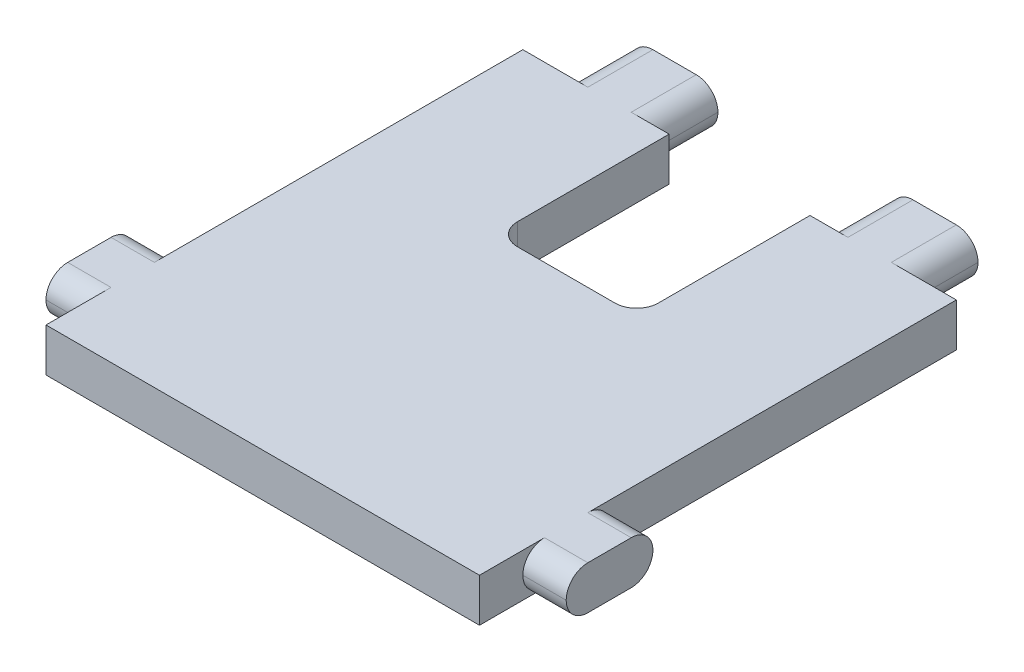
SolidWorks part; units mm, degrees
ref_plane "Front Plane" through (0, 0, 0) normal (0, 0, 1) x (1, 0, 0)
ref_plane "Top Plane" through (0, 0, 0) normal (0, 1, 0) x (1, 0, 0)
ref_plane "Right Plane" through (0, 0, 0) normal (1, 0, 0) x (0, 0, -1)
sketch "Sketch1" plane through (0, 0, 0) normal (0, 1, 0) x (1, 0, 0)
  line L0 (0, 11) -> (0, -11) construction
  line L1 (10, 11) -> (-10, 11)
  line L2 (10, 11) -> (10, -11)
  line L3 (10, -11) -> (-10, -11)
  line L4 (-10, 11) -> (-10, -11)
  line L5 (10, 11) -> (-10, -11) construction
  line L6 (10, -11) -> (-10, 11) construction
  line L15 (10, -9) -> (10, -5)
  line L21 (-3.25, 3) -> (3.25, 3)
  line L22 (-10, -9) -> (-12, -9)
  line L23 (-10, -9) -> (-10, -5)
  line L24 (-10, -5) -> (-12, -5)
  line L25 (-12, -9) -> (-12, -5)
  line L26 (10, -9) -> (12, -9)
  line L27 (12, -9) -> (12, -5)
  line L28 (10, -5) -> (12, -5)
  line L29 (-3.25, 3) -> (-3.25, 11)
  line L30 (-3.25, 11) -> (3.25, 11)
  line L31 (3.25, 3) -> (3.25, 11)
  line L32 (-3.25, 3) -> (3.25, 11) construction
  line L33 (-3.25, 11) -> (3.25, 3) construction
  line L41 (-6, 14) -> (-6, 11) construction
  line L42 (-4, 11) -> (-8, 11)
  line L43 (-4, 11) -> (-4, 14)
  line L44 (-4, 14) -> (-8, 14)
  line L45 (-8, 11) -> (-8, 14)
  line L46 (4, 11) -> (8, 11)
  line L47 (8, 11) -> (8, 14)
  line L48 (4, 14) -> (8, 14)
  line L49 (4, 11) -> (4, 14)
  point P0 (0, 0)
  point P14 (0, 7)
  dimension "D1" = 20
  dimension "D2" = 22
  dimension "D3" = 2
  dimension "D4" = 4
  dimension "D5" = 2
  dimension "D6" = 6.5
  dimension "D7" = 8
  dimension "D8" = 12
  dimension "D9" = 3
extrude "Boss-Extrude1" add sketch "Sketch1" along normal blind 2 contours L23 L4 | L1 L4 L3 L2 | L2 L15 | L31 L21 L29 L1 | L43 L1 | L1 region at (0, 0, 0.9381) region at (6, 0, -12.5) region at (11, 0, 7) region at (-6, 0, -12.5) region at (-11, 0, 7)
fillet "Fillet1" radius 1 18 edges at (11, 0, 5) (11, 2, 5) (11, 0, 9) (11, 2, 9) (-11, 0, 5) (-11, 2, 5) (-11, 0, 9) (-11, 2, 9) (-3.25, 1, -3) (3.25, 1, -3) (-8, 2, -12.5) (-8, 0, -12.5) (4, 0, -12.5) (4, 2, -12.5) (-4, 2, -12.5) (-4, 0, -12.5) (8, 0, -12.5) (8, 2, -12.5)
